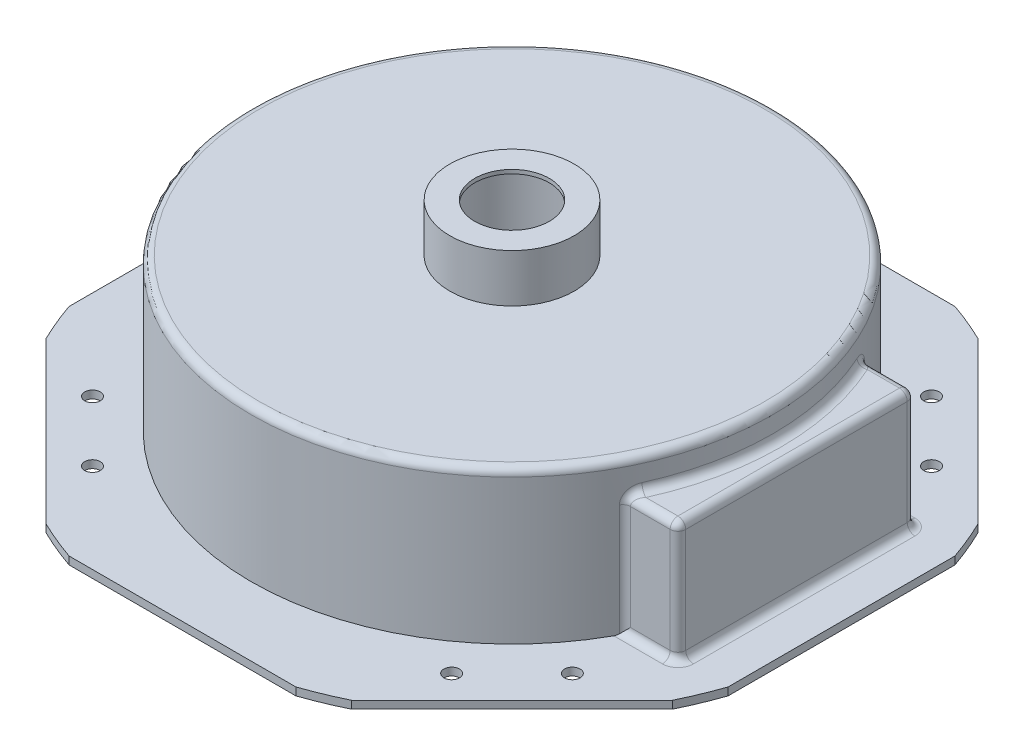
SolidWorks part; units mm, degrees
ref_plane "前视基准面" through (0, 0, 0) normal (0, 0, 1) x (1, 0, 0)
ref_plane "上视基准面" through (0, 0, 0) normal (0, 1, 0) x (1, 0, 0)
ref_plane "右视基准面" through (0, 0, 0) normal (1, 0, 0) x (0, 0, -1)
sketch "草图1" plane through (0, 0, 0) normal (0, 1, 0) x (1, 0, 0)
  line L1 (423.95, -175.6058) -> (423.95, 175.6058)
  line L2 (423.95, 175.6058) -> (175.6058, 423.95)
  line L3 (175.6058, 423.95) -> (-175.6058, 423.95)
  line L4 (-175.6058, 423.95) -> (-423.95, 175.6058)
  line L5 (-423.95, 175.6058) -> (-423.95, -175.6058)
  line L6 (-423.95, -175.6058) -> (-175.6058, -423.95)
  line L7 (-175.6058, -423.95) -> (175.6058, -423.95)
  line L8 (175.6058, -423.95) -> (423.95, -175.6058)
  circle A0 centre (0, 0) radius 423.95 construction
  circle A1 centre (0, 0) radius 448.35
  dimension "D2" = 896.7
  dimension "D1" = 847.9
extrude "凸台-拉伸1" add sketch "草图1" along normal blind 10 contours L7 A1 L8 L1 L2 L3 L4 L5 L6 region at (0, 0, 0)
sketch "草图2" plane through (0, 10, 0) normal (0, 1, 0) x (1, 0, 0)
  circle A0 centre (0, 0) radius 335.5
  dimension "D1" = 671
extrude "凸台-拉伸2" add sketch "草图2" along normal blind 196 separate body
sketch "草图3" plane through (0, 10, 0) normal (0, 1, 0) x (1, 0, 0)
  line L0 (0, 0) -> (423.95, 0) construction
  line L1 (423.95, -145.8908) -> (423.95, 145.8908) construction
  line L2 (366, 152.5) -> (366, -152.5)
  line L3 (366, 152.5) -> (298.8377, 152.5)
  line L4 (366, -152.5) -> (298.8377, -152.5)
  circle A1 centre (0, 0) radius 335.5 construction
  arc A2 (298.8377, -152.5) -> (298.8377, 152.5) centre (0, 0) ccw
  point P10 (366, 0)
  dimension "D1" = 305
  dimension "D2" = 366
extrude "凸台-拉伸3" add sketch "草图3" along normal blind 154.8 separate body
combine bodies "组合1" operation type add bodies to combine 107 108
shell "抽壳1" thickness 5 removed face at (173.8344, 10, 0)
sketch "草图4" plane through (0, 10, 0) normal (0, -1, 0) x (1, 0, 0)
  line L2 (366, -152.5) -> (298.8377, -152.5) construction
  line L3 (366, 152.5) -> (366, -152.5) construction
  line L4 (298.8377, 152.5) -> (366, 152.5) construction
  line L5 (366, -152.5) -> (298.8377, -152.5) construction
  line L6 (366, 152.5) -> (366, -152.5) construction
  line L7 (298.8377, 152.5) -> (366, 152.5) construction
  line L8 (361, -147.5) -> (295.76, -147.5)
  line L9 (361, 147.5) -> (361, -147.5)
  line L10 (295.76, 147.5) -> (361, 147.5)
  arc A2 (298.8377, 152.5) -> (298.8377, -152.5) centre (0, 0) ccw construction
  arc A3 (298.8377, 152.5) -> (298.8377, -152.5) centre (0, 0) ccw construction
  arc A4 (295.76, 147.5) -> (295.76, -147.5) centre (0, 0) ccw
  dimension "D1" = 5
extrude "切除-拉伸1" cut sketch "草图4" along normal blind 196
combine bodies "组合2" operation type add bodies to combine 110 109
sketch "草图5" plane through (0, 206, 0) normal (0, 1, 0) x (1, 0, 0)
  circle A0 centre (0, 0) radius 80
  dimension "D1" = 160
extrude "凸台-拉伸4" add sketch "草图5" along normal offset from surface (61.8 mm away) 267.8 up to face at (0, 0, 0)
extrude "凸台-拉伸5" add sketch "草图5<2>" against normal offset from surface (128.6 mm away) 77.4 up to face at (0, 0, 0)
sketch "草图5<2>" plane through (0, 206, 0) normal (0, 1, 0) x (1, 0, 0) same geometry as "草图5"
sketch "草图6" plane through (0, 77.4, 0) normal (0, -1, 0) x (1, 0, 0)
  circle A2 centre (0, 0) radius 75
  circle A3 centre (0, 0) radius 75
  dimension "D1" = 5
extrude "切除-拉伸2" cut sketch "草图6" against normal offset from surface (185.4 mm away) 5 up to face at (0, 267.8, 80)
sketch "草图7" plane through (0, 10, 0) normal (0, 1, 0) x (1, 0, 0)
  line L0 (-231.0613, 308.7016) -> (-308.7016, 231.0613) construction
  line L2 (-196.6176, 402.9383) -> (-402.9383, 196.6176) construction
  line L3 (-269.8814, 269.8814) -> (-299.7779, 299.7779) construction
  circle A0 centre (-231.0613, 308.7016) radius 10
  circle A1 centre (-308.7016, 231.0613) radius 10
  dimension "D1" = 20
  dimension "D2" = 42.28
  dimension "D3" = 109.8
extrude "切除-拉伸3" cut sketch "草图7" against normal blind 25
pattern_circular "阵列(圆周)1" count 4 over 360 about axis through (0, 206, 0) along (0, -1, 0) of "切除-拉伸3" reverse direction yes
sketch "草图8" plane through (0, 0, 0) normal (0, 0, 1) x (1, 0, 0)
  line L0 (-80, 82.4) -> (-335.5, 104.7534)
  line L1 (-80, 201) -> (-80, 77.4) construction
  line L2 (-335.5, 206) -> (-335.5, 10) construction
  line L3 (-80, 201) -> (-80, 77.4) construction
  dimension "D1" = 5
  dimension "D2" = 85
rib "筋1" sketch "草图8" sketch "草图8" thickness 10 extrusion direction parallel to sketch draft on no parameters "D1"=10
pattern_circular "阵列(圆周)2" count 6 over 360 about axis through (0, -226.2742, 0) along (0, 1, 0) skipping 3 of "筋1" reverse direction yes
sketch "草图9" plane through (0, 0, 0) normal (0, 0, 1) x (1, 0, 0)
  line L0 (80, 77.4) -> (80, 201) construction
  line L1 (80, 77.4) -> (80, 201) construction
  line L2 (80, 82.4) -> (330.5, 164.8)
  line L3 (335.5, 164.8) -> (335.5, 206) construction
  line L4 (335.5, 164.8) -> (335.5, 206) construction
  line L5 (335.5, 164.8) -> (330.5, 164.8) construction
  line L6 (366, 164.8) -> (298.8377, 164.8) construction
  dimension "D1" = 5
  dimension "D2" = 5
rib "筋2" sketch "草图9" sketch "草图9" thickness 10 extrusion direction parallel to sketch draft on no parameters "D1"=10
sketch "草图10" plane through (0, 267.8, 0) normal (0, 1, 0) x (1, 0, 0)
  circle A0 centre (0, 0) radius 48
  dimension "D1" = 96
extrude "切除-拉伸4" cut sketch "草图10" against normal through all
fillet "圆角1" radius 10 12 edges at (366, 10, 0) (335.5, 164.8, 0) (366, 164.8, 0) (366, 87.4, -152.5) (332.4189, 164.8, -152.5) (298.8377, 87.4, -152.5) (332.4189, 10, -152.5) (298.8377, 87.4, 152.5) (332.4189, 164.8, 152.5) (366, 87.4, 152.5) (332.4189, 10, 152.5) (0, 206, 335.5)
